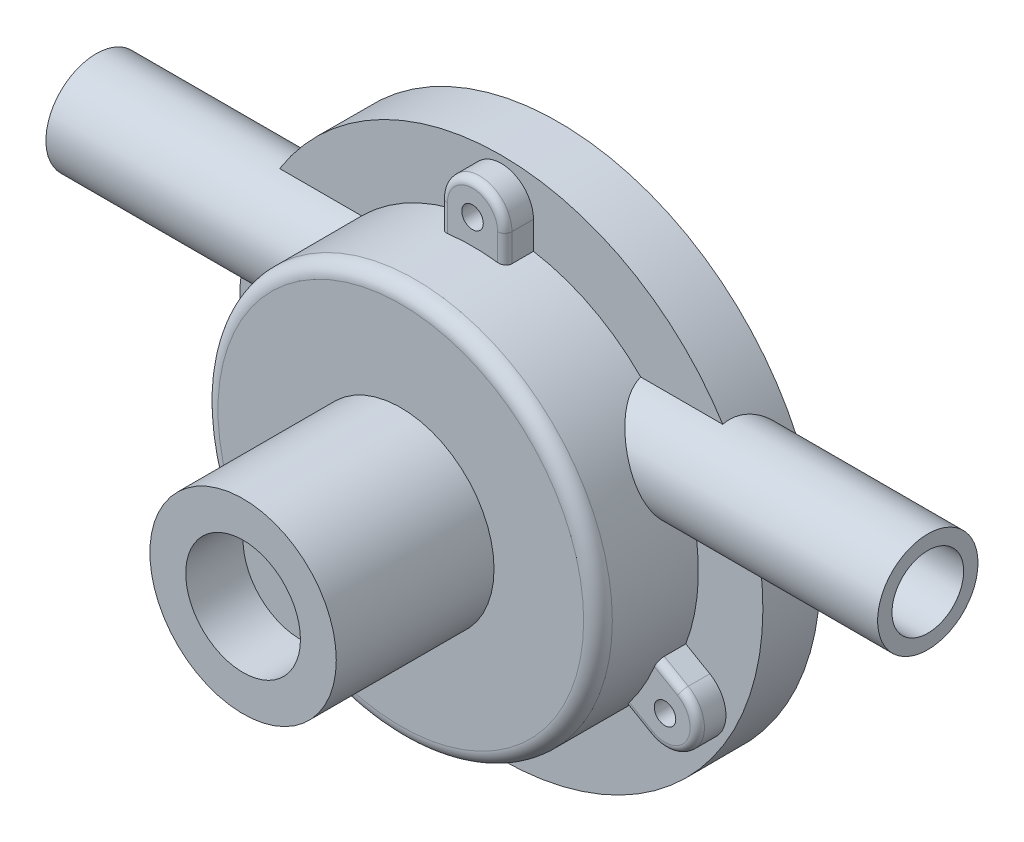
SolidWorks part; units mm, degrees
ref_plane "Front Plane" through (0, 0, 0) normal (0, 0, 1) x (1, 0, 0)
ref_plane "Top Plane" through (0, 0, 0) normal (0, 1, 0) x (1, 0, 0)
ref_plane "Right Plane" through (0, 0, 0) normal (1, 0, 0) x (0, 0, -1)
sketch "Sketch1" plane through (0, 0, 0) normal (0, 0, 1) x (1, 0, 0)
  circle A0 centre (0, 0) radius 36.5
  dimension "D1" = 73
extrude "Boss-Extrude1" add sketch "Sketch1" along normal blind 8
sketch "Sketch2" plane through (0, 0, 8) normal (0, 0, 1) x (1, 0, 0)
  circle A0 centre (0, 0) radius 27.5
  dimension "D1" = 55
extrude "Boss-Extrude2" add sketch "Sketch2" along normal blind 14
sketch "Sketch3" plane through (0, 0, 22) normal (0, 0, 1) x (1, 0, 0)
  circle A0 centre (0, 0) radius 13
  dimension "D1" = 26
extrude "Boss-Extrude3" add sketch "Sketch3" along normal blind 22
sketch "Sketch4" plane through (0, 0, 44) normal (0, 0, 1) x (1, 0, 0)
  circle A0 centre (0, 0) radius 8
  dimension "D1" = 16
extrude "Cut-Extrude1" cut sketch "Sketch4" against normal blind 8
ref_plane "Plane2" through (36.5, 0, 0) normal (1, 0, 0) x (0, 0, -1)
sketch "Sketch6" plane through (36.5, 0, 0) normal (1, 0, 0) x (0, 0, -1)
  line L0 (0, -36.5) -> (0, 36.5) construction
  line L2 (-8, 27.5) -> (-22, 27.5) construction
  circle A0 centre (-7, 12.5) radius 7
  dimension "D1" = 14
  dimension "D2" = 7
  dimension "D3" = 15
extrude "Boss-Extrude4" add sketch "Sketch6" along normal blind 22 and the other way blind 94
sketch "Sketch8" plane through (0, 0, 0) normal (0, 0, -1) x (-1, 0, 0)
  circle A1 centre (0, 0) radius 8 construction
  arc A3 (-17.6535, 13.95) -> (17.6535, 13.95) centre (0, 0) ccw
  arc A4 (-17.6535, 13.95) -> (17.6535, 13.95) centre (0, -22.5) cw
  point P2 (0, -8)
  dimension "D1" = 45
  dimension "D2" = 40.5
extrude "Cut-Extrude2" cut sketch "Sketch8" against normal blind 12
sketch "Sketch10" plane through (58.5, 0, 0) normal (1, 0, 0) x (0, 0, -1)
  circle A0 centre (-7, 12.5) radius 5
  dimension "D1" = 10
sketch "Sketch11" plane through (0, 0, 0) normal (0, 0, -1) x (-1, 0, 0)
  circle A0 centre (0, 31) radius 1.5
  circle A1 centre (0, 0) radius 36.5 construction
  circle A7 centre (26.8468, -15.5) radius 1.5
  circle A8 centre (-26.8468, -15.5) radius 1.5
  arc A9 (-34.2929, 12.5) -> (34.2929, 12.5) centre (0, 0) ccw construction
  point P13 (0, -1)
  point P14 (0, 0)
  point P15 (0, -1)
  dimension "D1" = 3
  dimension "D3" = 3
  dimension "D4" = 26.8468
  dimension "D5" = 31
  dimension "D2" = 31
extrude "Cut-Extrude4" cut sketch "Sketch11" against normal through all
fillet "Fillet1" radius 2 1 edges at (27.5, 0, 22)
extrude "Cut-Extrude5" cut sketch "Sketch10" against normal through all
sketch "Sketch12" plane through (0, 0, 36) normal (0, 0, 1) x (1, 0, 0)
  circle A0 centre (0, 0) radius 3.2
  dimension "D1" = 6.4
extrude "Cut-Extrude6" cut sketch "Sketch12" against normal through all
sketch "Sketch13" plane through (0, 0, 0) normal (0, 0, -1) x (-1, 0, 0)
  circle A0 centre (0, 0) radius 25
  circle A1 centre (0, 0) radius 27.3
extrude "Cut-Extrude7" cut sketch "Sketch13" against normal blind 1.2
sketch "Sketch14" plane through (0, 0, 8) normal (0, 0, 1) x (1, 0, 0)
  line L0 (4.5, 31) -> (4.5, 27.1293)
  line L1 (-4.5, 31) -> (-4.5, 27.1293)
  line L2 (29.0968, -11.6029) -> (25.7447, -9.6675)
  line L3 (24.5968, -19.3971) -> (21.2447, -17.4618)
  line L4 (-24.5968, -19.3971) -> (-21.2447, -17.4618)
  line L5 (-29.0968, -11.6029) -> (-25.7447, -9.6675)
  arc A2 (4.5, 31) -> (-4.5, 31) centre (0, 31) ccw
  arc A3 (19.4627, 19.4282) -> (-19.4627, 19.4282) centre (0, 0) ccw construction
  arc A4 (24.5968, -19.3971) -> (29.0968, -11.6029) centre (26.8468, -15.5) ccw
  arc A5 (-29.0968, -11.6029) -> (-24.5968, -19.3971) centre (-26.8468, -15.5) ccw
  arc A6 (21.2447, -17.4618) -> (25.7447, -9.6675) centre (0, 0) ccw
  arc A7 (-25.7447, -9.6675) -> (-21.2447, -17.4618) centre (0, 0) ccw
  arc A8 (4.5, 27.1293) -> (-4.5, 27.1293) centre (0, 0) ccw
  point P27 (0, 0)
  dimension "D1" = 9
  dimension "D2" = 3
extrude "Boss-Extrude5" add sketch "Sketch14" along normal blind 4
fillet "Fillet2" radius 1 9 edges at (4.5, 29.0647, 12) (-4.5, 29.0647, 12) (22.9207, -18.4294, 12) (27.4207, -10.6352, 12) (-27.4207, -10.6352, 12) (-22.9207, -18.4294, 12) (0, 35.5, 12) (30.7439, -17.75, 12) (-30.7439, -17.75, 12)
sketch "Sketch15" plane through (0, 0, 0) normal (0, 0, -1) x (-1, 0, 0)
  circle A0 centre (0, 31) radius 1.5
  circle A1 centre (26.8468, -15.5) radius 1.5
  circle A2 centre (-26.8468, -15.5) radius 1.5
  point P10 (0, 0)
  dimension "D1" = 3
  dimension "D4" = 26.8468
  dimension "D3" = 15.5
  dimension "D2" = 3
extrude "Cut-Extrude8" cut sketch "Sketch15" against normal through all
